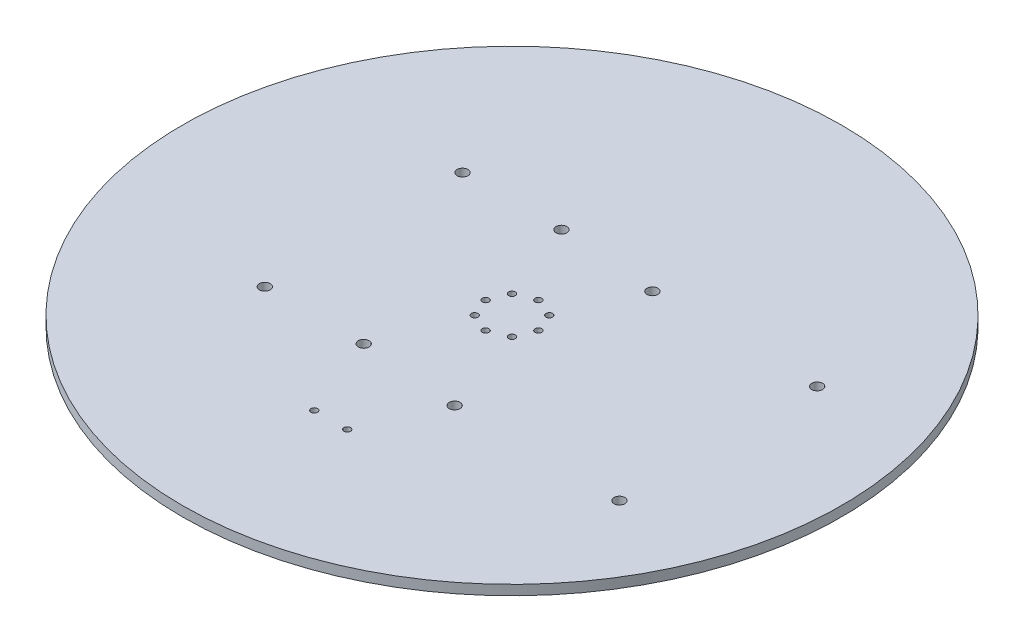
SolidWorks part; units mm, degrees
material "ABS"
ref_plane "Front Plane" through (0, 0, 0) normal (0, 0, 1) x (1, 0, 0)
ref_plane "Top Plane" through (0, 0, 0) normal (0, 1, 0) x (1, 0, 0)
ref_plane "Right Plane" through (0, 0, 0) normal (1, 0, 0) x (0, 0, -1)
sketch "Sketch2" plane through (0, 0, 0) normal (0, 1, 0) x (1, 0, 0)
  circle A0 centre (0, 0) radius 100
  dimension "D1" = 200
extrude "Boss-Extrude1" add sketch "Sketch2" along normal blind 3
sketch "Sketch3" plane through (0, 0, 0) normal (0, -1, 0) x (1, 0, 0)
  circle A0 centre (0, 75) radius 10
  dimension "D1" = 75
  dimension "D2" = 20
extrude "Boss-Extrude2" add sketch "Sketch3" along normal blind 4.75
sketch "Sketch4" plane through (0, 0, 0) normal (0, 0, 1) x (1, 0, 0)
  line L0 (0, 3) -> (0, -49997) construction
  line L1 (100, 3) -> (-100, 3) construction
  point P4 (0, 3)
pattern_circular "CirPattern1" count 5 over 360 about axis through (0, 3, 0) along (0, -1, 0) of "Boss-Extrude2"
fillet "Fillet3" radius 10 5 edges at (0, -4.75, 65) (61.8187, -4.75, 20.0861) (38.206, -4.75, -52.5861) (-38.206, -4.75, -52.5861) (-61.8187, -4.75, 20.0861)
sketch "Sketch5" plane through (0, 0, 0) normal (0, -1, 0) x (1, 0, 0)
  line L1 (-0.75, -9.5) -> (0.75, -9.5)
  line L2 (-0.75, -9.5) -> (-0.75, -12.5)
  line L3 (-0.75, -12.5) -> (0.75, -12.5)
  line L4 (0.75, -9.5) -> (0.75, -12.5)
  line L5 (-0.75, -9.5) -> (0.75, -12.5) construction
  line L6 (-0.75, -12.5) -> (0.75, -9.5) construction
  circle A0 centre (0, 0) radius 11
  circle A1 centre (0, 8) radius 1
  circle A2 centre (5.6569, 5.6569) radius 1
  circle A3 centre (8, 0) radius 1
  circle A4 centre (5.6569, -5.6569) radius 1
  circle A5 centre (0, -8) radius 1
  circle A6 centre (-5.6569, -5.6569) radius 1
  circle A7 centre (-8, 0) radius 1
  circle A8 centre (-5.6569, 5.6569) radius 1
  point P5 (0, -11)
  point P22 (0, 0)
  dimension "D1" = 22
  dimension "D2" = 2
  dimension "D3" = 8
  dimension "D5" = 8
  dimension "D6" = 1.5
  dimension "D7" = 3
  dimension "D4" = 8
extrude "Cut-Extrude1" cut sketch "Sketch5" against normal up to surface (3 mm away) contours A8 | A1 | A2 | A3 | A4 | A5 | A6 | A7 up to face at (0, 3, 100)
extrude "Boss-Extrude3" add sketch "Sketch5<3>" along normal blind 3 contours L2 A0 L4 L1 | A0 L2 L3 L4 region at (0, 0, -10.2458) region at (0, 0, -11.7457)
sketch "Sketch5<3>" plane through (0, 0, 0) normal (0, -1, 0) x (1, 0, 0) same geometry as "Sketch5"
sketch "Sketch6" plane through (0, 3, 0) normal (0, 1, 0) x (1, 0, 0)
  line L1 (-45, 30) -> (-15, 30)
  line L2 (-45, 30) -> (-45, -30)
  line L3 (-45, -30) -> (-15, -30)
  line L4 (-15, 30) -> (-15, -30)
  circle A0 centre (-45, 30) radius 2
  circle A1 centre (-15, 30) radius 2
  circle A2 centre (-15, -30) radius 2
  circle A3 centre (-45, -30) radius 2
  point P4 (-15, 0)
  dimension "D4" = 4
  dimension "D1" = 30
  dimension "D2" = 60
  dimension "D3" = 15
  dimension "D5" = 2
  dimension "D6" = 2
hole_wizard "Tap Drill for M4x0.7 Tap1" positions "3DSketch1" profile "Sketch7" hole size "M4x0.7" standard "ANSI Metric" end condition up to next
sketch3d "3DSketch1"
  point P0 (-45, 3, -30)
  point P3 (-15, 3, -30)
  point P6 (-45, 3, 30)
  point P9 (-15, 3, 30)
sketch "Sketch7" plane through (-45, 3, -30) normal (1, 0, 0) x (0, 0, 1)
  line L0 (0, 0) -> (0, 3)
  line L1 (0, 3) -> (1.65, 3)
  line L2 (1.65, 3) -> (1.65, 0)
  line L5 (1.65, 0) -> (0, 0)
  line L11 (0, -6.35) -> (0, 107.95) construction
  dimension "Thru Hole Dia." = 3.3
  dimension "Thru Hole Depth" = 3
sketch "Sketch8" plane through (0, 3, 0) normal (0, 1, 0) x (1, 0, 0)
  line L5 (-15, 30) -> (-15, -30) construction
  line L7 (15, 27.6) -> (65, 27.6)
  line L8 (15, 27.6) -> (15, -32.4)
  line L9 (15, -32.4) -> (65, -32.4)
  line L10 (65, 27.6) -> (65, -32.4)
  line L13 (-45, 30) -> (-15, 30) construction
  line L14 (13.9, -16) -> (65, -16)
  line L15 (13.9, -13.75) -> (13.9, -18.25) construction
  circle A0 centre (15, 27.6) radius 2
  circle A1 centre (65, 27.6) radius 2
  circle A2 centre (15, -32.4) radius 2
  circle A3 centre (65, -32.4) radius 2
  dimension "D4" = 4
  dimension "D5" = 4
  dimension "D6" = 4
  dimension "D7" = 4
  dimension "D1" = 50
  dimension "D2" = 60
  dimension "D3" = 30
  dimension "D8" = 2.4
  dimension "D9" = 2.9021
hole_wizard "Tap Drill for M4x0.7 Tap2" positions "3DSketch2" profile "Sketch9" hole size "M4x0.7" standard "ANSI Metric" end condition up to next
sketch3d "3DSketch2"
  point P0 (15, 3, -27.6)
  point P3 (15, 3, 32.4)
  point P6 (65, 3, 32.4)
  point P9 (65, 3, -27.6)
sketch "Sketch9" plane through (15, 3, -27.6) normal (1, 0, 0) x (0, 0, 1)
  line L0 (0, 0) -> (0, 3)
  line L1 (0, 3) -> (1.65, 3)
  line L2 (1.65, 3) -> (1.65, 0)
  line L5 (1.65, 0) -> (0, 0)
  line L11 (0, -6.35) -> (0, 107.95) construction
  dimension "Thru Hole Dia." = 3.3
  dimension "Thru Hole Depth" = 3
sketch "Sketch10" plane through (0, 3, 0) normal (0, 1, 0) x (1, 0, 0)
  line L0 (0, 0) -> (0, 100) construction
  line L1 (-5, -55) -> (5, -55)
  line L2 (-5, -55) -> (-5, -65)
  line L3 (-5, -65) -> (5, -65)
  line L4 (5, -55) -> (5, -65)
  line L5 (0, -55) -> (0, -65) construction
  circle A0 centre (-5, -65) radius 1
  circle A1 centre (5, -65) radius 1
  circle A2 centre (5, -55) radius 1
  circle A3 centre (-5, -55) radius 1
  circle A4 centre (0, 0) radius 100 construction
  dimension "D3" = 2
  dimension "D4" = 2
  dimension "D5" = 2
  dimension "D6" = 2
  dimension "D1" = 10
  dimension "D2" = 10
  dimension "D7" = 65
extrude "Cut-Extrude2" cut sketch "Sketch10" against normal through all contours A3 | A2
